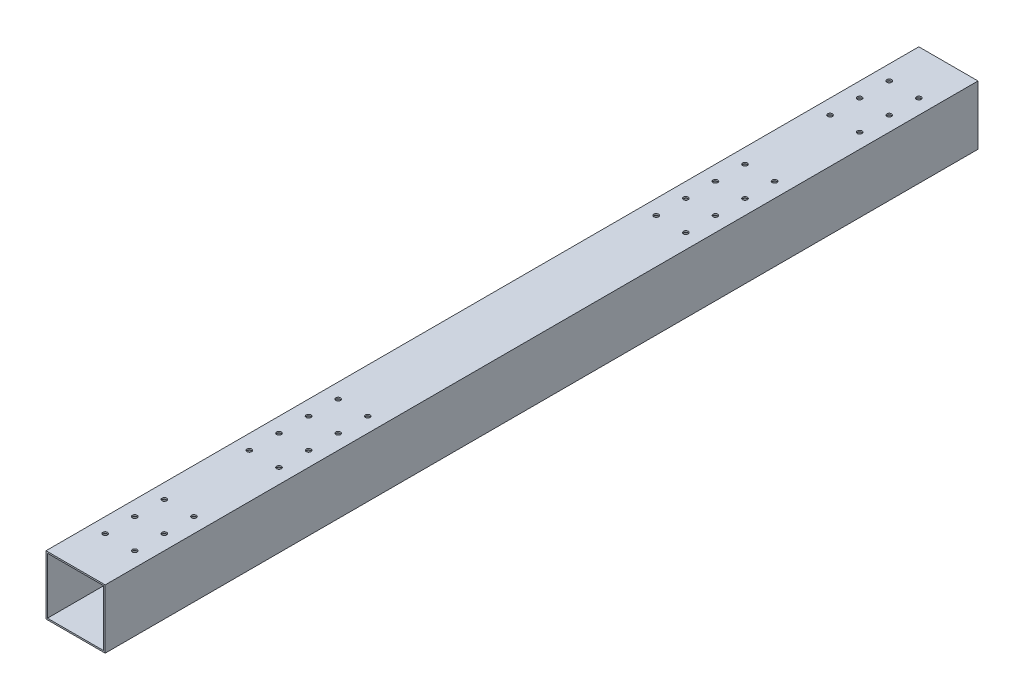
SolidWorks part; units mm, degrees
material "6061 合金"
ref_plane "前视基准面" through (0, 0, 0) normal (0, 0, 1) x (1, 0, 0)
ref_plane "上视基准面" through (0, 0, 0) normal (0, 1, 0) x (1, 0, 0)
ref_plane "右视基准面" through (0, 0, 0) normal (1, 0, 0) x (0, 0, -1)
other "Configuration Table"
sketch "草图1" plane through (0, 0, 0) normal (0, 0, 1) x (1, 0, 0)
  line L1 (-20, 20) -> (20, 20)
  line L2 (-20, 20) -> (-20, -20)
  line L3 (-20, -20) -> (20, -20)
  line L4 (20, 20) -> (20, -20)
  line L5 (-20, 20) -> (20, -20) construction
  line L6 (-20, -20) -> (20, 20) construction
  line L7 (-19, 19) -> (19, 19)
  line L8 (-19, 19) -> (-19, -19)
  line L9 (-19, -19) -> (19, -19)
  line L10 (19, 19) -> (19, -19)
  line L11 (-19, 19) -> (19, -19) construction
  line L12 (-19, -19) -> (19, 19) construction
  point P0 (0, 0)
  point P6 (0, 0)
  dimension "D1" = 40
  dimension "D2" = 1
extrude "凸台-拉伸1" add sketch "草图1" along normal mid plane 590
sketch "草图2" plane through (0, 20, 0) normal (0, 1, 0) x (1, 0, 0)
  line L0 (0, -290) -> (0, -50290) construction
  line L1 (20, -295) -> (-20, -295) construction
  line L2 (-10, -167.5) -> (-10, -147.5) construction
  line L3 (0, 0) -> (50000, 0) construction
  circle A0 centre (-10, -167.5) radius 1.6
  circle A1 centre (10, -167.5) radius 1.6
  circle A2 centre (-10, -147.5) radius 1.6
  circle A3 centre (10, -147.5) radius 1.6
  circle A4 centre (-10, -127.5) radius 1.6
  circle A5 centre (10, -127.5) radius 1.6
  circle A6 centre (-10, -107.5) radius 1.6
  circle A7 centre (10, -107.5) radius 1.6
  circle A8 centre (10, 107.5) radius 1.6
  circle A9 centre (-10, 107.5) radius 1.6
  circle A10 centre (10, 127.5) radius 1.6
  circle A11 centre (-10, 127.5) radius 1.6
  circle A12 centre (10, 147.5) radius 1.6
  circle A13 centre (-10, 147.5) radius 1.6
  circle A14 centre (10, 167.5) radius 1.6
  circle A15 centre (-10, 167.5) radius 1.6
  point P4 (0, -295)
  dimension "D1" = 20
  dimension "D2" = 3.2
  dimension "D3" = 107.5
  dimension "D5" = 20
  dimension "D4" = 4
extrude "切除-拉伸1" cut sketch "草图2" against normal through all
sketch "草图3" plane through (0, 20, 0) normal (0, 1, 0) x (1, 0, 0)
  circle A0 centre (-10, 225) radius 1.6 construction
  circle A1 centre (10, 225) radius 1.6 construction
  circle A2 centre (10, 245) radius 1.6 construction
  circle A3 centre (-10, 245) radius 1.6 construction
  circle A4 centre (-10, 265) radius 1.6 construction
  circle A5 centre (10, 265) radius 1.6 construction
  circle A6 centre (-10, 225) radius 1.6
  circle A7 centre (10, 225) radius 1.6
  circle A8 centre (10, 245) radius 1.6
  circle A9 centre (-10, 245) radius 1.6
  circle A10 centre (-10, 265) radius 1.6
  circle A11 centre (10, 265) radius 1.6
  circle A12 centre (10, -265) radius 1.6 construction
  circle A13 centre (-10, -265) radius 1.6 construction
  circle A14 centre (-10, -245) radius 1.6 construction
  circle A15 centre (10, -245) radius 1.6 construction
  circle A16 centre (10, -225) radius 1.6 construction
  circle A17 centre (-10, -225) radius 1.6 construction
  circle A18 centre (10, -265) radius 1.6
  circle A19 centre (-10, -265) radius 1.6
  circle A20 centre (-10, -245) radius 1.6
  circle A21 centre (10, -245) radius 1.6
  circle A22 centre (10, -225) radius 1.6
  circle A23 centre (-10, -225) radius 1.6
extrude "切除-拉伸2" cut sketch "草图3" against normal up to next
